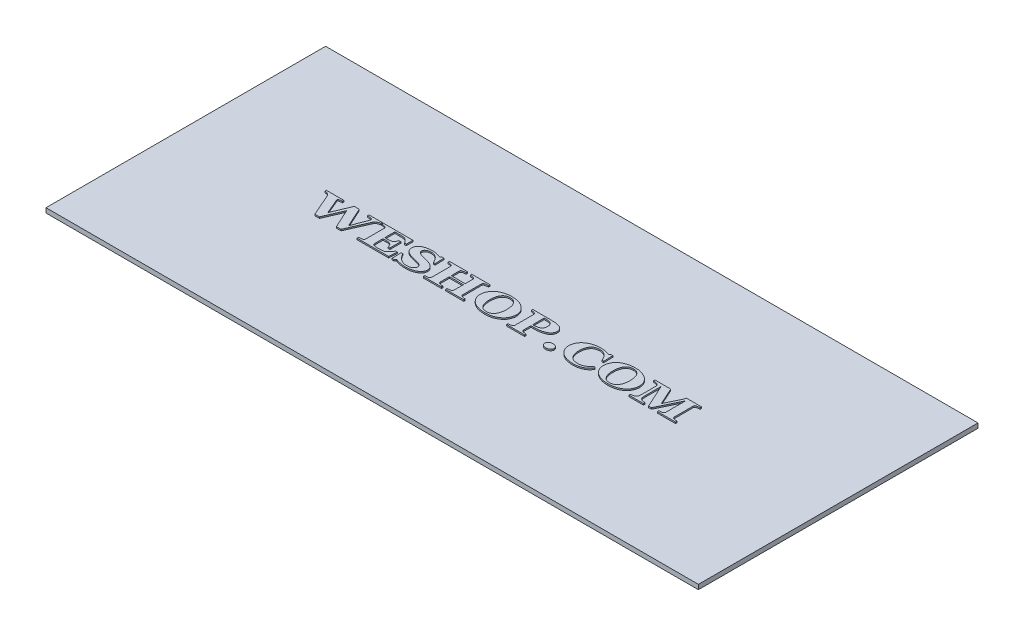
SolidWorks part; units mm, degrees
ref_plane "Front" through (0, 0, 0) normal (0, 0, 1) x (1, 0, 0)
ref_plane "Top" through (0, 0, 0) normal (0, 1, 0) x (1, 0, 0)
ref_plane "Right" through (0, 0, 0) normal (1, 0, 0) x (0, 0, -1)
sketch "Sketch1" plane through (0, 0, 0) normal (0, 1, 0) x (1, 0, 0)
  line L1 (0, 0) -> (280, 0)
  line L2 (0, 0) -> (0, -120)
  line L3 (0, -120) -> (280, -120)
  line L4 (280, 0) -> (280, -120)
  dimension "D1" = 120
  dimension "D2" = 280
extrude "Boss-Extrude1" add sketch "Sketch1" along normal blind 2
sketch "Sketch2" plane through (0, 2, 0) normal (0, 1, 0) x (1, 0, 0)
  text T0 "<b>WESHOP.COM</b>\r\n" font "Georgia" height in points 42
  point P1 (0, 0)
  point P2 (0, 0)
extrude "Boss-Extrude2" add sketch "Sketch2" along normal blind 0.6
